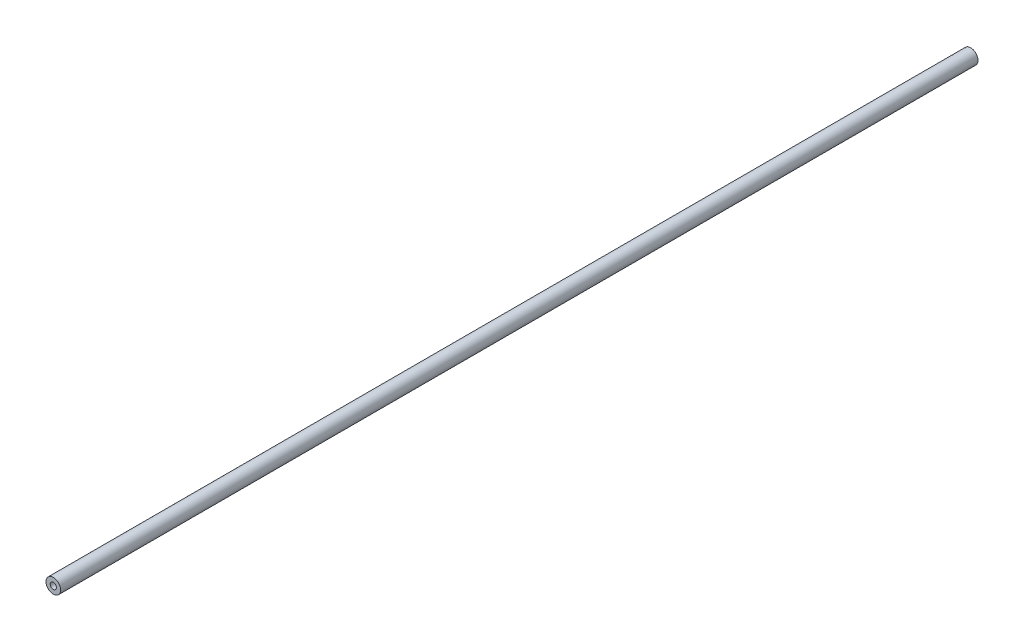
SolidWorks part; units mm, degrees
material "7075-T6, Plate (SS)"
ref_plane "Front Plane" through (0, 0, 0) normal (0, 0, 1) x (1, 0, 0)
ref_plane "Top Plane" through (0, 0, 0) normal (0, 1, 0) x (1, 0, 0)
ref_plane "Right Plane" through (0, 0, 0) normal (1, 0, 0) x (0, 0, -1)
sketch "Sketch1" plane through (0, 0, 0) normal (0, 0, 1) x (1, 0, 0)
  circle A1 centre (0, 0) radius 4.7625
  dimension "D1" = 9.525
extrude "Boss-Extrude1" add sketch "Sketch1" against normal blind 596.9
sketch "Sketch5" plane through (0, 0, -596.9) normal (0, 0, -1) x (-1, 0, 0)
  point P0 (0, 0)
hole_wizard "#10-32 Tapped Hole1" positions "Sketch5" profile "Sketch6" tap size "#10-32" standard "ANSI Inch"
sketch "Sketch6" plane through (0, 0, -596.9) normal (1, 0, 0) x (0, 1, 0)
  line L0 (0, 0) -> (0, 20.2633)
  line L1 (0, 20.2633) -> (2.0193, 19.05)
  line L2 (2.0193, 19.05) -> (2.0193, 0)
  line L5 (2.0193, 0) -> (0, 0)
  line L10 (0, 20.2633) -> (-2.0193, 19.05) construction
  line L11 (0, -6.35) -> (0, 107.95) construction
  dimension "Tap Drill Dia." = 4.0386
  dimension "Tap Drill Depth" = 19.05
  dimension "Drill Angle" = 118
cosmetic thread "Hole Thread1"
hole_wizard "#10-32 Tapped Hole4" positions "Sketch11" profile "Sketch12" tap size "#10-32" standard "ANSI Inch"
sketch "Sketch11" plane through (0, 0, 0) normal (0, 0, 1) x (1, 0, 0)
  point P0 (0, 0)
sketch "Sketch12" plane through (0, 0, 0) normal (1, 0, 0) x (0, -1, 0)
  line L0 (0, 0) -> (0, 20.2633)
  line L1 (0, 20.2633) -> (2.0193, 19.05)
  line L2 (2.0193, 19.05) -> (2.0193, 0)
  line L5 (2.0193, 0) -> (0, 0)
  line L10 (0, 20.2633) -> (-2.0193, 19.05) construction
  line L11 (0, -6.35) -> (0, 107.95) construction
  dimension "Tap Drill Dia." = 4.0386
  dimension "Tap Drill Depth" = 19.05
  dimension "Drill Angle" = 118
cosmetic thread "Hole Thread4"
